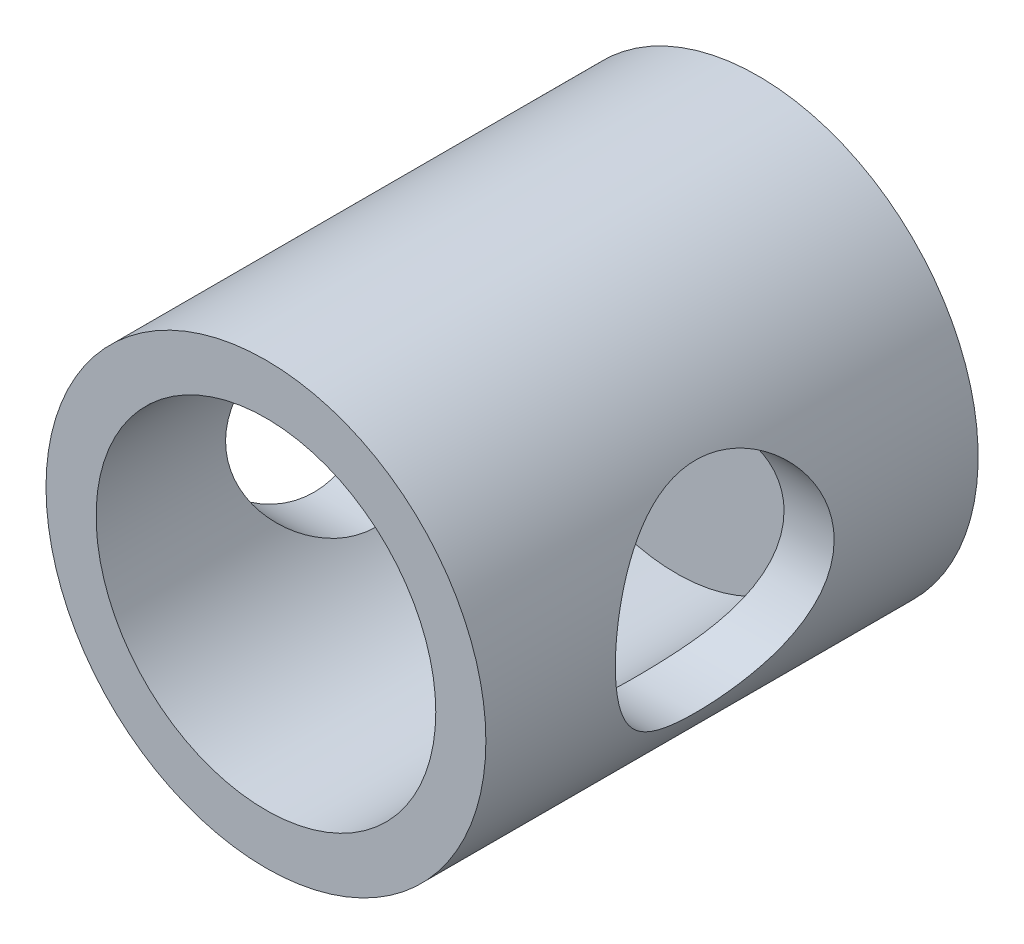
SolidWorks part; units mm, degrees
ref_plane "Front Plane" through (0, 0, 0) normal (0, 0, 1) x (1, 0, 0)
ref_plane "Top Plane" through (0, 0, 0) normal (0, 1, 0) x (1, 0, 0)
ref_plane "Right Plane" through (0, 0, 0) normal (1, 0, 0) x (0, 0, -1)
sketch "Sketch2" plane through (0, 0, 0) normal (0, 0, 1) x (1, 0, 0)
  circle A0 centre (0, 0) radius 10
  dimension "D1" = 20
extrude "Boss-Extrude1" add sketch "Sketch2" along normal blind 18
sketch "Sketch5" plane through (0, 0, 0) normal (1, 0, 0) x (0, 0, -1)
  circle A0 centre (-9.266, 0) radius 4
  dimension "D1" = 8
extrude "Cut-Extrude1" cut sketch "Sketch5" along normal blind 18 and the other way blind 21
sketch "Sketch6" plane through (0, 0, 0) normal (0, 0, -1) x (-1, 0, 0)
  circle A0 centre (0, 0) radius 8.0421
  point P3 (0, 0)
extrude "Cut-Extrude2" cut sketch "Sketch6" against normal blind 24 flip side to cut contours A0
sketch "Sketch8" plane through (0, 0, 18) normal (0, 0, 1) x (1, 0, 0)
  circle A0 centre (0, 0) radius 6.2103
extrude "Cut-Extrude4" cut sketch "Sketch8" against normal blind 15 contours A0
